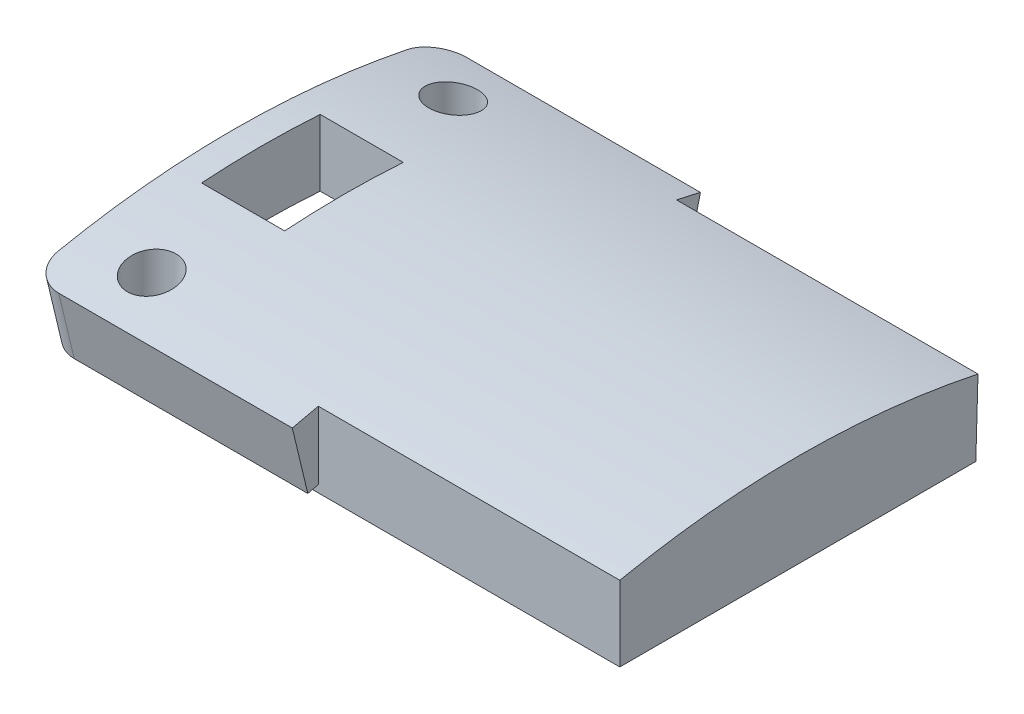
SolidWorks part; units mm, degrees
ref_plane "Front Plane" through (0, 0, 0) normal (0, 0, 1) x (1, 0, 0)
ref_plane "Top Plane" through (0, 0, 0) normal (0, 1, 0) x (1, 0, 0)
ref_plane "Right Plane" through (0, 0, 0) normal (1, 0, 0) x (0, 0, -1)
sketch "Sketch1" plane through (0, 0, 0) normal (0, 0, 1) x (1, 0, 0)
  line L0 (21.581, -73.66) -> (-66.7143, -73.66) construction
  line L1 (-11.1125, -5.588) -> (11.1125, -5.588)
  line L2 (11.1125, -5.588) -> (11.1125, 0)
  line L3 (11.1125, 0) -> (-11.1125, 0)
  line L4 (-11.1125, 0) -> (-11.1125, -5.588)
  dimension "D1" = 73.66
  dimension "D2" = 5.588
  dimension "D3" = 22.225
revolve "Revolve1" add sketch "Sketch1" angle 27 mid plane about L0
sketch "Sketch2" plane through (0, 0, 0) normal (0, 1, 0) x (1, 0, 0)
  line L0 (-11.1125, 17.1956) -> (-11.1125, -17.1956) construction
  line L1 (-1.7313, -5) -> (-8.7312, -5)
  line L2 (-1.7313, -5) -> (-1.7313, 5)
  line L3 (-1.7313, 5) -> (-8.7312, 5)
  line L4 (-8.7312, -5) -> (-8.7312, 5)
  line L5 (-1.7313, -5) -> (-8.7312, 5) construction
  line L6 (-1.7313, 5) -> (-8.7312, -5) construction
  line L7 (11.1125, -17.1956) -> (11.1125, 17.1956) construction
  line L8 (-11.1125, 17.1956) -> (-11.1125, -17.1956)
  line L9 (11.1125, -17.1956) -> (11.1125, 17.1956)
  line L10 (-11.1125, 0) -> (11.1125, 0) construction
  circle A1 centre (-5.2313, 12.7) radius 2.05
  circle A2 centre (-5.2313, -12.7) radius 2.05
  point P0 (-5.2313, 0)
  dimension "D6" = 4.1
  dimension "D1" = 10
  dimension "D2" = 7
  dimension "D4" = 2.3813
  dimension "D7" = 12.7
extrude "Cut-Extrude1" cut sketch "Sketch2" against normal through all contours L4 L1 L2 L3 | A1 | A2 region at (-5.2313, 0, 0)
ref_plane "Plane1" through (3.3487, 0, 0) normal (-1, 0, 0) x (0, 0, 1)
shell "Shell2" [suppressed] thickness 1.905
sketch "Sketch5" [suppressed] plane through (9.2075, 0, 0) normal (-1, 0, 0) x (0, 0, 1)
  line L2 (3.383, -0.1219) -> (3.383, -5.7264)
  line L6 (8.8642, -6.548) -> (10.3118, -1.1454)
  line L7 (8.8642, -6.548) -> (10.3118, -1.1454)
  line L8 (3.383, -0.1219) -> (3.383, -5.7264)
  arc A2 (8.8642, -6.548) -> (3.383, -5.7264) centre (0, -46.99) ccw
  arc A3 (8.8642, -6.548) -> (3.383, -5.7264) centre (0, -46.99) ccw
  arc A6 (10.3118, -1.1454) -> (3.383, -0.1219) centre (0, -46.99) ccw
  arc A7 (10.3118, -1.1454) -> (3.383, -0.1219) centre (0, -46.99) ccw
  dimension "D1" = 0
extrude "Cut-Extrude2" [suppressed] cut sketch "Sketch5" against normal through all
fillet "Fillet1" [suppressed] radius 2.54
fillet "Fillet2" radius 2.54 2 edges at (-11.1125, -4.752, -16.5433) (-11.1125, -4.752, 16.5433)
sketch "Sketch8" plane through (11.1125, 0, 0) normal (1, 0, 0) x (0, 0, -1)
  line L2 (-15, -7.874) -> (15, -7.874)
  line L5 (-15, -7.874) -> (-15, -1.5435)
  line L6 (15, -7.874) -> (15.1846, -1.5821)
  arc A0 (17.1956, -2.0352) -> (-17.1956, -2.0352) centre (0, -73.66) ccw construction
  arc A1 (15.1846, -1.5821) -> (-15, -1.5435) centre (0, -73.66) ccw
  point P0 (0, -7.874)
  dimension "D1" = 30
  dimension "D2" = 7.874
extrude "Boss-Extrude2" add sketch "Sketch8" along normal blind 25.4 and the other way blind 1.27
hole_wizard "#24 (0.152) Diameter Hole1" positions "Sketch9" profile "Sketch10" hole size "#24" standard "ANSI Inch"
sketch "Sketch9" plane through (0, -7.874, 0) normal (0, -1, 0) x (-1, 0, 0)
  line L2 (1.7313, -5) -> (1.7313, 5) construction
  point P0 (-32.2687, 11.5)
  point P2 (-32.2687, -11.5)
  dimension "D1" = 23
  dimension "D2" = 11.5
  dimension "D3" = 34
sketch "Sketch10" plane through (32.2687, -7.874, -11.5) normal (1, 0, 0) x (0, 0, -1)
  line L0 (0, 0) -> (0, 4.5599)
  line L1 (0, 4.5599) -> (1.9304, 3.4)
  line L2 (1.9304, 3.4) -> (1.9304, 0)
  line L5 (1.9304, 0) -> (0, 0)
  line L10 (0, 4.5599) -> (-1.9304, 3.4) construction
  line L11 (0, -6.35) -> (0, 107.95) construction
  dimension "Hole Dia." = 3.8608
  dimension "Hole Depth" = 3.4
  dimension "Drill Angle" = 118
sketch "Sketch12" plane through (9.8425, 0, 0) normal (-1, 0, 0) x (0, 0, 1)
  circle A0 centre (-23.333, -17.3422) radius 9
  dimension "D1" = 18
extrude "Cut-Extrude3" [suppressed] cut sketch "Sketch12" against normal blind 24
sketch "Sketch13" [suppressed] plane through (33.8425, 0, 0) normal (-1, 0, 0) x (0, 0, 1)
  circle A0 centre (-23.333, -17.3422) radius 9
  arc A1 (-19.6767, -9.1184) -> (-31.734, -14.1138) centre (-23.333, -17.3422) ccw construction
extrude "Boss-Extrude3" [suppressed] add sketch "Sketch13" against normal up to surface (2.67 mm away)
fillet "Fillet3" [suppressed] radius 2.54
sketch "Sketch14" [suppressed] plane through (9.8425, 0, 0) normal (-1, 0, 0) x (0, 0, 1)
  line L0 (-40.4766, -12.1178) -> (-37.0776, -17.2858)
  line L1 (-15, -7.874) -> (-17.2354, -2.0448)
  arc A0 (-13.4235, -1.2334) -> (-40.4766, -12.1178) centre (0, -73.66) ccw construction
  arc A1 (-40.4766, -12.1178) -> (-17.2354, -2.0448) centre (0, -73.66) cw
  arc A2 (-37.0776, -17.2858) -> (-31.734, -14.1138) centre (0, -73.66) cw
  arc A3 (-31.734, -14.1138) -> (-37.0776, -17.2858) centre (0, -73.66) ccw construction
  arc A4 (-31.734, -14.1138) -> (-19.6767, -9.1184) centre (-23.333, -17.3422) cw
  arc A5 (-19.6767, -9.1184) -> (-31.734, -14.1138) centre (-23.333, -17.3422) ccw construction
  arc A6 (-19.6767, -9.1184) -> (-15, -7.874) centre (0, -73.66) cw
  arc A7 (-15, -7.874) -> (-19.6767, -9.1184) centre (0, -73.66) ccw construction
extrude "Boss-Extrude4" [suppressed] add sketch "Sketch14" along normal blind 20
sketch "Sketch16" [suppressed] plane through (33.8425, 0, 0) normal (-1, 0, 0) x (0, 0, 1)
  line L0 (-27.4395, -19.0436) -> (-24.4441, -26.2734)
  line L1 (-19.2265, -15.6408) -> (-16.2311, -22.8706)
  line L2 (-23.333, -17.3422) -> (0, -73.66) construction
  arc A0 (-19.2265, -15.6408) -> (-27.4395, -19.0436) centre (-23.333, -17.3422) ccw
  circle A1 centre (-23.333, -17.3422) radius 9 construction
  arc A2 (-16.2311, -22.8706) -> (-24.4441, -26.2734) centre (-23.333, -17.3422) cw
  circle A3 centre (0, -73.66) radius 73.66 construction
  arc A4 (-17.2354, -2.0448) -> (-40.4766, -12.1178) centre (0, -73.66) ccw construction
  dimension "D1" = 8.89
extrude "Cut-Extrude4" [suppressed] cut sketch "Sketch16" against normal through all
fillet "Fillet5" [suppressed] radius 0.254
equation "\"Mid_Coupler_ID\"= 3.7"
equation "\"Thiccness\"= 5.5mm"
equation "\"Bracket_Angle\"= 27"
equation "\"D1@Revolve1\"=\"Bracket_Angle\""
equation "\"Cam_Slot_Width\"= 10mm"
equation "\"Cam_Slot_Length\"= 7mm"
equation "\"D1@Sketch2\"=\"Cam_Slot_Width\""
equation "\"D2@Sketch2\"=\"Cam_Slot_Length\""
equation "\"Screw_Angle\"= 12.5deg"
equation "\"M3_Insert_OD\"= 4.1mm"
equation "\"Length\"= ( 7 / 8 ) * 1in"
equation "\"D3@Sketch1\"=\"Length\""
equation "\"Mid_Tube_Length\"= 1in"
equation "\"Bodytube_OD\" = 6.17in"
equation "\"Bodytube_ID\" = 5.998in"
equation "\"Camera_Cutout_Width\"=10mm"
equation "\"Camera_Cutout_Height\"=7mm"
equation "\"Fwd_Tube_Length\" = 38.5in"
equation "\"BKHD_Screw_Diam\"= 3.5mm"
equation "\"Fwd_BKHD_From_Top\" = 18in"
equation "\"Shear_Screw_Diameter\" = 0.086in"
equation "\"Shear_Screw_Coupler_Location\" = 4.5in"
equation "\"Motor_OD\" = 4in"
equation "\"Mid_Coupler_Length\" = 13in"
equation "\"Aft_Section_Length\"= 36in"
equation "\"AB_Coupler_OD_Length\"= 1in"
equation "\"AB_Coupling_Section_Length\"= 0.375in"
equation "\"AB_Coupler_Length\"= \"AB_Coupler_OD_Length\" + \"AB_Coupling_Section_Length\" * 2"
equation "\"Cutout_Angle\" = 80"
equation "\"AB_Paddle_Height\" = 0.375in"
equation "\"AB_Coupler_Num_Screws\"= 4"
equation "\"AB_BKHD_Thickness\" = 0.375in"
equation "\"AB_Mount_From_Bottom\" = 23.175in"
equation "\"Num_Cutouts\" = 3"
equation "\"AB_Coupler_OD\"= 6.17in"
equation "\"AB_Coupler_ID\"= 5.75in"
equation "\"AB_Coupler_Surface_Diameter\"= 5.998in"
equation "\"AB_Coupling_Screw_Diameter\"= 0.15748in"
equation "\"AB_Central_Bushing_Length\" = .4724in"
equation "\"Lead_Screw_Dist\" = 3.4in"
equation "\"Lead_Screw_Diam\" = 0.386in"
equation "\"Lead_Screw_Length\" = (\"Mid_Coupler_Length\" + 2*0.375in + 2*.75in)"
equation "\"Paddle_Pin_Offset\" = .25in"
equation "\"Paddle_Pin_Radius\" = 2.25in"
equation "\"SS_Paddle_Pin_Radius\" = 2.25*0.66in"
equation "\"Paddle_Gear_OD\" = 3.2in"
equation "\"Drive_Gear_OD\" = 1.7in"
equation "\"Fin_Thickness\"= .118in"
equation "\"Guiderail_Cutout_Diameter\"= 1.5in"
equation "\"DB9_Hole_Dist\" = 25mm"
equation "\"DB9_Relief_Width\" = 0.47in"
equation "\"DB9_Relief_Hole_Offset\" = 0.09in"
equation "\"Airbrakes_Wire_Hole_Dia\" = .25in"
equation "\"Airbrakes_Wire_Hole_Dist\" = 1.1in"
equation "\"Servo_Gear_Offset\" = 0.5in"
equation "\"FWD_Shear_Screw_Dist\" = 1.5in"
equation "\"Camera_Screw_Dia\" = 0.216535"
equation "\"Camera_Hole_Angle\" = atn ( 2 / 3 * tan ( 12.5deg ) )"
equation "\"Coupler_OD\" = 5.998"
equation "\"Coupler_ID\" = 5.8"
equation "\"D1@Sketch3\"=\"Camera_Hole_Angle\"/2"
equation "\"D2@Sketch3\"=2*\"Thiccness\""
equation "\"D3@Sketch3\"=\"M3_Insert_OD\"/2"
